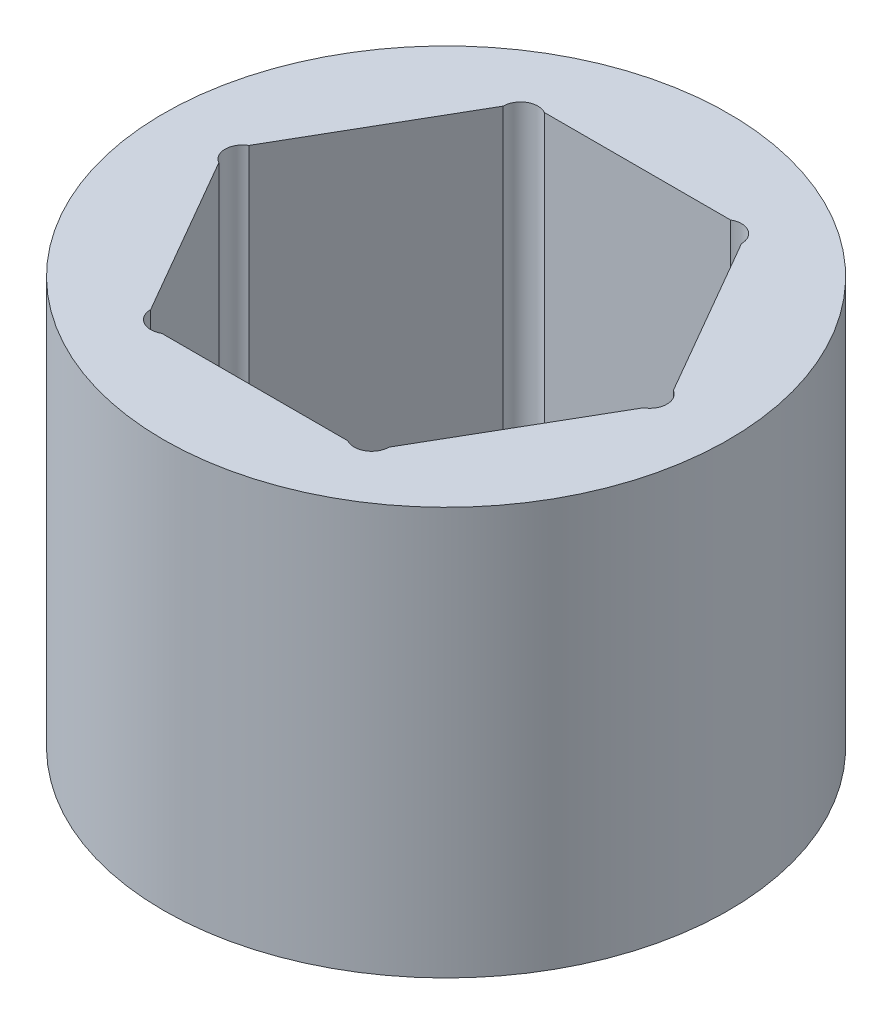
SolidWorks part; units mm, degrees
ref_plane "Front Plane" through (0, 0, 0) normal (0, 0, 1) x (1, 0, 0)
ref_plane "Top Plane" through (0, 0, 0) normal (0, 1, 0) x (1, 0, 0)
ref_plane "Right Plane" through (0, 0, 0) normal (1, 0, 0) x (0, 0, -1)
sketch "Sketch1" plane through (0, 0, 0) normal (0, 1, 0) x (1, 0, 0)
  line L0 (0, 0) -> (3.8128, 6.604) construction
  line L1 (7.6256, 0) -> (3.8128, 6.604)
  line L2 (3.8128, 6.604) -> (-3.8128, 6.604)
  line L3 (-3.8128, 6.604) -> (-7.6256, 0)
  line L4 (-7.6256, 0) -> (-3.8128, -6.604)
  line L5 (-3.8128, -6.604) -> (3.8128, -6.604)
  line L6 (3.8128, -6.604) -> (7.6256, 0)
  circle A0 centre (0, 0) radius 6.604 construction
  circle A1 centre (0, 0) radius 9.7536
  circle A2 centre (3.5128, 6.0844) radius 0.6
  circle A3 centre (7.0256, 0) radius 0.6
  circle A4 centre (3.5128, -6.0844) radius 0.6
  circle A5 centre (-3.5128, -6.0844) radius 0.6
  circle A6 centre (-7.0256, 0) radius 0.6
  circle A7 centre (-3.5128, 6.0844) radius 0.6
  point P25 (0, 0)
  dimension "D1" = 13.208
  dimension "D2" = 19.5072
  dimension "D3" = 1.2
  dimension "D4" = 6
extrude "Boss-Extrude1" add sketch "Sketch1" along normal blind 14.0716 contours A1 A7 L2 A2 L1 A3 L6 A4 L5 A5 L4 A6 L3 region at (-9.4777, 0, 0)
